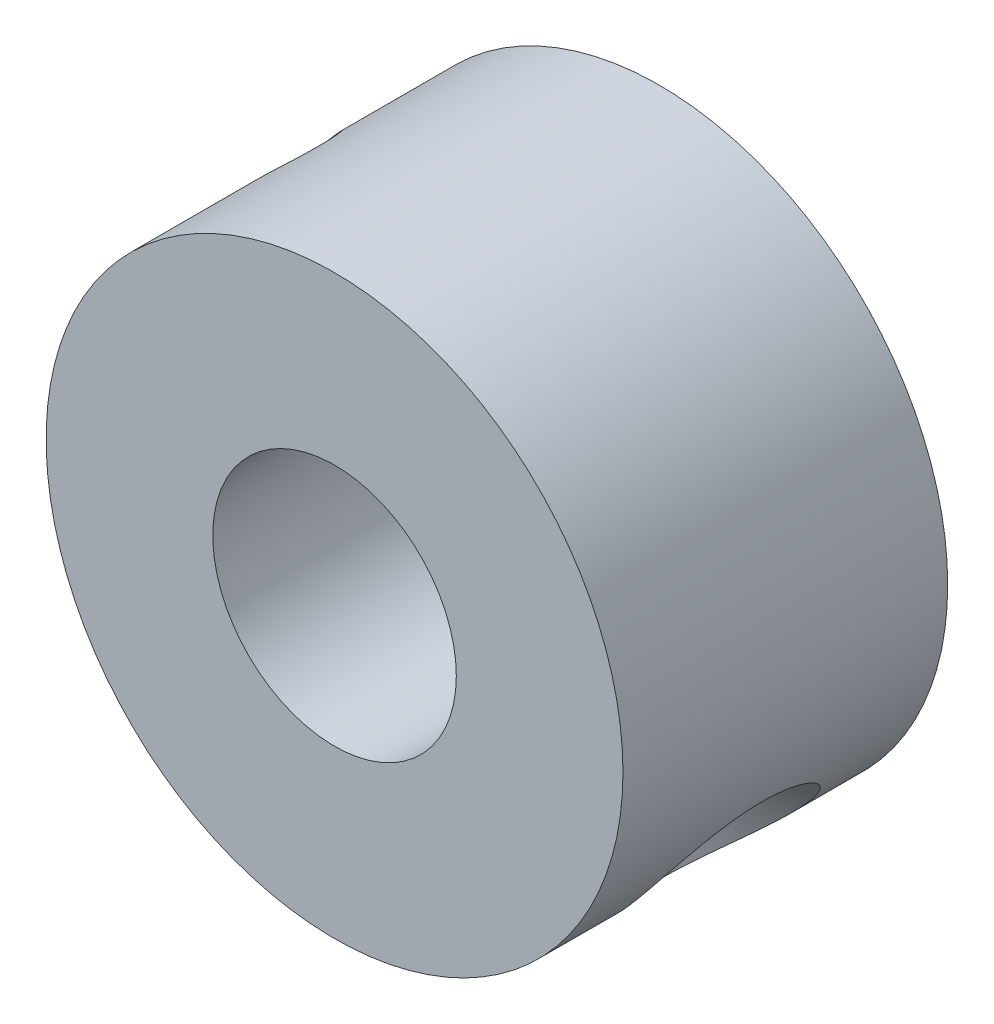
SolidWorks part; units mm, degrees
ref_plane "Front Plane" through (0, 0, 0) normal (0, 0, 1) x (1, 0, 0)
ref_plane "Top Plane" through (0, 0, 0) normal (0, 1, 0) x (1, 0, 0)
ref_plane "Right Plane" through (0, 0, 0) normal (1, 0, 0) x (0, 0, -1)
sketch "Sketch1" plane through (0, 0, 0) normal (0, 0, 1) x (1, 0, 0)
  circle A0 centre (0, 0) radius 7.1054
  circle A1 centre (0, 0) radius 3
extrude "Boss-Extrude3" add sketch "Sketch1" along normal blind 8 contours A1 | A0 region at (0, 0, 0)
sketch "Sketch2" plane through (0, 0, 8) normal (0, 0, 1) x (1, 0, 0)
  circle A0 centre (0, 0) radius 5
  circle A1 centre (0, 0) radius 3
hole_wizard "CSK for M2 Flat Head Machine Screw2" positions "3DSketch4" profile "Sketch6" countersink size "M2" standard "ANSI Metric" end condition through all
sketch3d "3DSketch4"
  point P0 (5.372, -4.6507, 3.8937)
sketch "Sketch6" plane through (5.372, -4.6507, 3.8937) normal (0, 0, 1) x (0.6545, 0.756, 0)
  line L0 (0, 0) -> (0, 17.1281)
  line L1 (0, 17.1281) -> (1.2, 17.1281)
  line L2 (1.2, 17.1281) -> (1.2, 1)
  line L3 (1.2, 1) -> (2.2, 0)
  line L5 (2.2, 0) -> (0, 0)
  line L6 (-1.2, 1) -> (-2.2, 0) construction
  line L11 (0, -6.35) -> (0, 107.95) construction
  dimension "Thru Hole Dia." = 2.4
  dimension "Thru Hole Depth" = 17.1281
  dimension "Near C'Sink Dia." = 4.4
  dimension "Near C'Sink Angle" = 90
